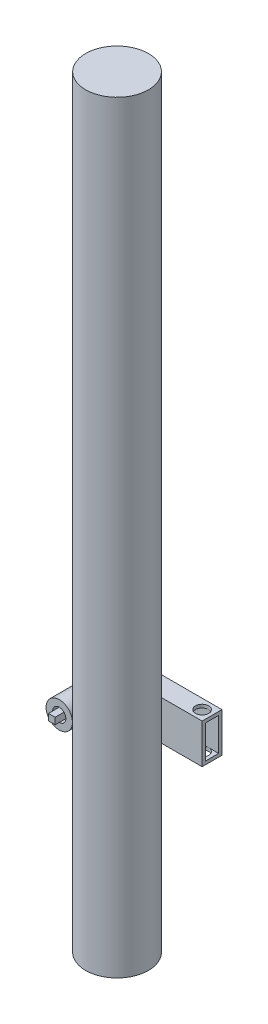
SolidWorks part; units mm, degrees
ref_plane "Front Plane" through (0, 0, 0) normal (0, 0, 1) x (1, 0, 0)
ref_plane "Top Plane" through (0, 0, 0) normal (0, 1, 0) x (1, 0, 0)
ref_plane "Right Plane" through (0, 0, 0) normal (1, 0, 0) x (0, 0, -1)
sketch "Elevation Bar" plane through (0, 0, 0) normal (0, 1, 0) x (1, 0, 0)
  circle A0 centre (0, 0) radius 30.226
  dimension "D1" = 60.452
extrude "Elevation Bar Part" add sketch "Elevation Bar" along normal blind 734.06
sketch "Pole and Drivetrain Pos" plane through (0, 0, 0) normal (0, 0, 1) x (1, 0, 0)
  line L0 (0, 0) -> (172.1794, 0) construction
  line L1 (-30.226, 0) -> (-30.226, 734.06) construction
  line L2 (-30.226, 734.06) -> (30.226, 734.06) construction
  line L3 (30.226, 734.06) -> (30.226, 0) construction
  line L4 (30.226, 0) -> (30.226, 734.06) construction
  line L5 (636.651, 41.275) -> (27.051, 41.275) construction
  line L6 (636.651, 53.975) -> (27.051, 53.975)
  line L7 (636.651, 53.975) -> (636.651, 28.575)
  line L8 (636.651, 28.575) -> (27.051, 28.575)
  line L9 (27.051, 53.975) -> (27.051, 28.575)
  line L10 (-30.226, 93.98) -> (30.226, 93.98) construction
  line L11 (33.2486, 0) -> (-33.2486, 0) construction
  line L12 (30.226, 185.42) -> (-30.226, 185.42) construction
  line L13 (30.226, 276.86) -> (-30.226, 276.86) construction
  line L14 (30.226, 368.3) -> (-30.226, 368.3) construction
  line L15 (30.226, 459.74) -> (-30.226, 459.74) construction
  line L16 (30.226, 551.18) -> (-30.226, 551.18) construction
  line L17 (30.226, 642.62) -> (-30.226, 642.62) construction
  line L18 (30.226, 73.152) -> (750.8896, 73.152) construction
  circle A0 centre (579.501, 41.275) radius 41.275 construction
  circle A1 centre (84.201, 41.275) radius 41.275 construction
  circle A2 centre (331.851, 41.275) radius 41.275 construction
  circle A3 centre (84.201, 41.275) radius 25.4
  point P24 (331.851, 41.275)
  point P28 (0, 0)
  point P45 (0, 0)
  dimension "D2" = 82.55
  dimension "D5" = 50.8
  dimension "D1" = 609.6
  dimension "D3" = 25.4
  dimension "D6" = 93.98
  dimension "D7" = 185.42
  dimension "D8" = 276.86
  dimension "D9" = 368.3
  dimension "D10" = 459.74
  dimension "D11" = 551.18
  dimension "D12" = 642.62
  dimension "D13" = 73.152
  dimension "D14" = 57.15
  dimension "D4" = 57.15
  dimension "D15" = 6.35
sketch "Driving Wheels Geo" plane through (0, 0, 0) normal (0, 0, 1) x (1, 0, 0)
  line L0 (-30.226, 182.88) -> (-30.226, 101.727) construction
  line L1 (55.626, 101.727) -> (30.226, 101.727) construction
  line L2 (-30.226, 0) -> (-30.226, 734.06) construction
  line L3 (30.226, 734.06) -> (30.226, 0) construction
  line L5 (30.226, 101.727) -> (-30.226, 101.727) construction
  line L6 (-30.226, 182.88) -> (30.226, 101.727) construction
  line L7 (31.8135, 101.727) -> (-30.226, 182.88) construction
  line L8 (30.226, 227.417) -> (203.668, 53.975) construction
  line L9 (-42.926, 195.58) -> (44.8729, 195.58) construction
  line L10 (30.226, 73.152) -> (750.8896, 73.152) construction
  line L11 (636.651, 53.975) -> (27.051, 53.975) construction
  line L14 (-42.926, 170.18) -> (44.8729, 170.18) construction
  line L15 (44.8729, 170.18) -> (44.8729, 195.58) construction
  line L16 (81.026, 28.575) -> (81.026, 257.175) construction
  line L17 (32.1729, 195.58) -> (57.5729, 195.58) construction
  line L18 (32.1729, 195.58) -> (32.1729, 170.18) construction
  line L19 (32.1729, 170.18) -> (57.5729, 170.18) construction
  line L20 (57.5729, 195.58) -> (57.5729, 170.18) construction
  line L21 (32.1729, 195.58) -> (57.5729, 170.18) construction
  line L22 (32.1729, 170.18) -> (57.5729, 195.58) construction
  line L23 (636.651, 28.575) -> (27.051, 28.575) construction
  line L24 (284.226, 257.175) -> (81.026, 257.175) construction
  line L25 (284.226, 257.175) -> (284.226, 53.975) construction
  line L26 (81.026, 257.175) -> (30.226, 257.175) construction
  circle A1 centre (55.626, 101.727) radius 25.4
  circle A3 centre (-42.926, 182.88) radius 12.7
  circle A4 centre (81.026, 104.775) radius 50.8 construction
  circle A5 centre (55.626, 101.727) radius 23.8125 construction
  circle A7 centre (284.226, 257.175) radius 203.2 construction
  point P28 (44.8729, 182.88)
  dimension "D1" = 50.8
  dimension "D2" = 1.5875
  dimension "D3" = 52.603
  dimension "D4" = 3.175
  dimension "D5" = 182.88
  dimension "D8" = 101.6
  dimension "D6" = 25.4
  dimension "D13" = 3.175
  dimension "D14" = 50.8
  dimension "D16" = 406.4
  dimension "D7" = 81.153
  dimension "D9" = 45
  dimension "D10" = 53.317
  dimension "D11" = 25.4
  dimension "D12" = 47.752
ref_plane "Plane1" through (0, 182.88, 0) normal (0, 1, 0) x (1, 0, 0)
sketch "Clamp Geo" plane through (0, 182.88, 0) normal (0, 1, 0) x (1, 0, 0)
  line L0 (-42.926, -19.8438) -> (-42.926, 50.8635) construction
  line L3 (27.051, 228.6) -> (27.051, -228.6) construction
  line L4 (50.0464, 31.8135) -> (-49.276, 31.8135)
  line L5 (50.0464, 31.8135) -> (50.0464, 50.8635)
  line L6 (50.0464, 50.8635) -> (-49.276, 50.8635)
  line L7 (-49.276, 31.8135) -> (-49.276, 50.8635)
  line L10 (-46.101, 50.8635) -> (-39.751, 50.8635)
  line L11 (-46.101, 50.8635) -> (-46.101, -19.8438)
  line L12 (-46.101, -19.8438) -> (-39.751, -19.8438)
  line L13 (-39.751, 50.8635) -> (-39.751, -19.8438)
  line L14 (-55.626, 12.7) -> (-30.226, 12.7) construction
  line L15 (-55.626, 12.7) -> (-55.626, -12.7) construction
  line L16 (-55.626, -12.7) -> (-30.226, -12.7) construction
  line L17 (-30.226, 12.7) -> (-30.226, -12.7) construction
  line L18 (-55.626, 12.7) -> (-30.226, -12.7) construction
  line L19 (-55.626, -12.7) -> (-30.226, 12.7) construction
  line L20 (0, -30.226) -> (0, 30.226) construction
  line L21 (-30.226, 0) -> (30.226, 0) construction
  line L22 (-46.101, 46.101) -> (-42.926, 46.101) construction
  line L23 (-39.751, 41.3385) -> (-46.101, 41.3385)
  line L24 (-46.101, 41.3385) -> (-46.101, 50.8635) construction
  line L25 (-39.751, 31.8135) -> (-39.751, 50.8635) construction
  line L26 (50.0464, 41.3385) -> (40.5214, 41.3385) construction
  circle A0 centre (0, 0) radius 30.226 construction
  circle A3 centre (-42.926, 46.101) radius 1.8288
  circle A5 centre (-42.926, 36.576) radius 1.8288
  circle A6 centre (40.5214, 41.3385) radius 6.35
  circle A7 centre (40.5214, 41.3385) radius 13.4704 construction
  point P14 (-42.926, 0)
  point P32 (-39.751, 41.3385)
  point P34 (-46.101, 41.3385)
  point P36 (-42.926, 41.3385)
  point P42 (50.0464, 41.3385)
  dimension "D1" = 60.452
  dimension "D4" = 1.5875
  dimension "D7" = 3.6576
  dimension "D8" = 3.175
  dimension "D10" = 12.7
  dimension "D11" = 3.175
  dimension "D2" = 457.2
  dimension "D3" = 19.05
  dimension "D5" = 6.35
  dimension "D6" = 25.4
  dimension "D9" = 99.3224
  dimension "D13" = 7.1437
sketch "Locked Setting Geo" plane through (0, 182.88, 0) normal (0, 1, 0) x (1, 0, 0)
  line L0 (30.2525, 144.301) -> (91.1428, 108.3583) construction
  line L1 (27.477, 37.9778) -> (77.9656, 123.5104)
  line L2 (27.477, 37.9778) -> (43.8821, 28.2941)
  line L3 (43.8821, 28.2941) -> (94.3707, 113.8267)
  line L4 (77.9656, 123.5104) -> (94.3707, 113.8267)
  line L5 (92.7568, 111.0925) -> (89.5289, 105.6242)
  line L6 (92.7568, 111.0925) -> (31.8664, 147.0352)
  line L7 (31.8664, 147.0352) -> (28.6385, 141.5668)
  line L8 (89.5289, 105.6242) -> (28.6385, 141.5668)
  line L9 (64.7337, 138.6948) -> (51.8221, 116.8213) construction
  line L10 (64.7337, 138.6948) -> (42.8602, 151.6064) construction
  line L11 (42.8602, 151.6064) -> (29.9486, 129.7329) construction
  line L12 (51.8221, 116.8213) -> (29.9486, 129.7329) construction
  line L13 (64.7337, 138.6948) -> (29.9486, 129.7329) construction
  line L14 (42.8602, 151.6064) -> (51.8221, 116.8213) construction
  line L17 (88.6555, 113.5135) -> (87.0416, 110.7793) construction
  line L18 (81.3263, 110.466) -> (84.5542, 115.9344)
  line L19 (84.5542, 115.9344) -> (92.7568, 111.0925) construction
  line L20 (73.1238, 115.3079) -> (89.5289, 105.6242) construction
  line L21 (35.6795, 33.1359) -> (40.5214, 41.3385) construction
  line L22 (50.0464, 50.8635) -> (-49.276, 50.8635) construction
  line L23 (-46.101, 50.8635) -> (-46.101, -19.8438) construction
  line L24 (27.051, 228.6) -> (27.051, -228.6) construction
  circle A1 centre (87.0416, 110.7793) radius 1.8288
  circle A2 centre (78.839, 115.6211) radius 1.8288
  circle A3 centre (40.5214, 41.3385) radius 6.35
  point P10 (47.3411, 134.2138)
  point P28 (81.3263, 110.466)
  point P30 (84.5542, 115.9344)
  point P32 (82.9403, 113.2002)
  point P36 (35.6795, 33.1359)
  point P40 (40.5214, 41.3385)
  point P44 (-17.1792, 28.8062)
  dimension "D6" = 3.6576
  dimension "D9" = 12.7
  dimension "D2" = 19.05
  dimension "D3" = 1.5875
  dimension "D4" = 6.35
  dimension "D5" = 25.4
  dimension "D7" = 3.175
  dimension "D8" = 99.3224
  dimension "D10" = 3.175
  dimension "D11" = 50.8635
  dimension "D12" = 67.3197
extrude "Boss-Extrude1" add sketch "Clamp Geo" along normal blind 19.05 and the other way blind 19.05 separate body contours L6 L13 L4 L5 A6 | L11 L6 L7 L4 | L13 L23 L11 L4 A5 | L23 L13 L6 L11 A3 region at (2.3187, 182.88, -41.3385) region at (-42.926, 182.88, -31.928) region at (-47.6885, 182.88, -41.3385) region at (-42.926, 182.88, -41.453)
sketch "Sketch2" plane through (-49.276, 0, 0) normal (-1, 0, 0) x (0, 0, 1)
  line L0 (-41.3385, 201.93) -> (-41.3385, 163.83) construction
  line L1 (-31.8135, 201.93) -> (-50.8635, 201.93) construction
  line L2 (-31.8135, 163.83) -> (-50.8635, 163.83) construction
  line L3 (-31.8135, 163.83) -> (-31.8135, 201.93) construction
  line L4 (-47.6885, 167.005) -> (-34.9885, 167.005)
  line L5 (-47.6885, 167.005) -> (-47.6885, 198.755)
  line L6 (-47.6885, 198.755) -> (-34.9885, 198.755)
  line L7 (-34.9885, 167.005) -> (-34.9885, 198.755)
  line L8 (-47.6885, 167.005) -> (-34.9885, 198.755) construction
  line L9 (-47.6885, 198.755) -> (-34.9885, 167.005) construction
  point P6 (-41.3385, 182.88)
  dimension "D1" = 3.175
  dimension "D2" = 3.175
extrude "Cut-Extrude2" cut sketch "Sketch2" against normal up to surface (99.3224 mm away) up to face at (50.0464, 182.88, -41.3385)
sketch "Sketch3" plane through (0, 0, -50.8635) normal (0, 0, -1) x (-1, 0, 0)
  line L2 (39.7129, 179.6669) -> (46.1391, 179.6669)
  line L3 (39.7129, 179.6669) -> (39.7129, 186.0931)
  line L4 (39.7129, 186.0931) -> (46.1391, 186.0931)
  line L5 (46.1391, 179.6669) -> (46.1391, 186.0931)
  line L6 (39.7129, 179.6669) -> (46.1391, 186.0931) construction
  line L7 (39.7129, 186.0931) -> (46.1391, 179.6669) construction
  point P0 (42.926, 182.88)
  point P1 (42.926, 182.88)
  dimension "D1" = 6.4262
extrude "Cut-Extrude3" cut sketch "Sketch3" against normal up to surface (19.05 mm away) up to face at (0.3852, 182.88, -31.8135)
extrude "Boss-Extrude2" add sketch "Clamp Geo<3>" along normal blind 3.175 and the other way blind 3.175 separate body contours L13 L4 L11 L12 | L13 L23 L11 L4 A5 | L23 L13 L6 L11 A3 region at (-42.926, 182.88, -5.9849) region at (-42.926, 182.88, -31.928) region at (-42.926, 182.88, -41.453)
sketch "Clamp Geo<3>" plane through (0, 182.88, 0) normal (0, 1, 0) x (1, 0, 0) same geometry as "Clamp Geo"
sketch "Custom Driven Flywheel" plane through (0, 0, 0) normal (0, 0, 1) x (1, 0, 0)
  circle A0 centre (-42.926, 182.88) radius 12.7 construction
  circle A1 centre (-42.926, 182.88) radius 12.7
  circle A2 centre (-42.926, 182.88) radius 6.35
  dimension "D1" = 12.7
extrude "Boss-Extrude3" add sketch "Custom Driven Flywheel" along normal mid plane 25.4 separate body
sketch "Sketch8" plane through (0, 167.005, 0) normal (0, 1, 0) x (1, 0, 0)
  line L0 (-42.926, 47.6885) -> (-42.926, 34.9885) construction
  line L1 (-49.276, 34.9885) -> (-36.576, 34.9885) construction
  line L2 (-49.276, 34.9885) -> (-49.276, 47.6885)
  line L3 (-49.276, 47.6885) -> (-36.576, 47.6885) construction
  line L4 (-36.576, 34.9885) -> (-36.576, 47.6885)
  line L5 (-36.576, 41.3385) -> (-42.926, 41.3385) construction
  line L6 (-42.926, 41.3385) -> (-49.276, 41.3385) construction
  line L7 (-43.8339, 34.9885) -> (-49.276, 34.9885)
  line L8 (-43.8339, 47.6885) -> (-49.276, 47.6885)
  line L9 (-42.0181, 34.9885) -> (-36.576, 34.9885)
  line L10 (-42.0181, 47.6885) -> (-36.576, 47.6885)
  arc A0 (-43.8339, 47.6885) -> (-42.0181, 47.6885) centre (-42.926, 46.101) ccw construction
  arc A2 (-42.0181, 34.9885) -> (-43.8339, 34.9885) centre (-42.926, 36.576) ccw construction
  arc A3 (-43.8339, 47.6885) -> (-42.0181, 47.6885) centre (-42.926, 46.101) ccw
  arc A4 (-42.0181, 34.9885) -> (-43.8339, 34.9885) centre (-42.926, 36.576) ccw
extrude "Boss-Extrude5" add sketch "Sketch8" along normal up to surface (15.875 mm away) separate body up to plane "Plane1"
sketch "Sketch10" plane through (0, 182.88, 0) normal (0, 1, 0) x (1, 0, 0)
  line L0 (-36.576, 41.3385) -> (-49.276, 41.3385) construction
  line L1 (-36.576, 34.9885) -> (-36.576, 47.6885) construction
  line L2 (-49.276, 47.6885) -> (-49.276, 34.9885) construction
  line L3 (-49.276, 34.9885) -> (-43.8339, 34.9885) construction
  line L4 (-46.1391, 34.9885) -> (-39.7129, 34.9885)
  line L5 (-46.1391, 34.9885) -> (-46.1391, 47.6885)
  line L6 (-46.1391, 47.6885) -> (-39.7129, 47.6885)
  line L7 (-39.7129, 34.9885) -> (-39.7129, 47.6885)
  line L8 (-46.1391, 34.9885) -> (-39.7129, 47.6885) construction
  line L9 (-46.1391, 47.6885) -> (-39.7129, 34.9885) construction
  point P6 (-42.926, 41.3385)
  dimension "D1" = 6.4262
extrude "Cut-Extrude5" cut sketch "Sketch10" against normal blind 6.3881
ref_plane "Plane2" through (0, 0, 210.82) normal (0, 0, 1) x (1, 0, 0)
ref_plane "Plane3" through (0, 0, 166.37) normal (0, 0, 1) x (1, 0, 0)
sketch "Sketch12" plane through (0, 0, 166.37) normal (0, 0, 1) x (1, 0, 0)
  line L0 (636.651, 41.275) -> (27.051, 41.275) construction
  line L1 (636.651, 41.275) -> (27.051, 41.275) construction
  line L5 (636.651, 53.975) -> (27.051, 53.975) construction
  circle A0 centre (84.201, 41.275) radius 25.4 construction
  circle A1 centre (84.201, 41.275) radius 25.4
  circle A2 centre (55.626, 101.727) radius 21.1667
  circle A4 centre (83.7633, 116.4361) radius 10.5833
  circle A5 centre (128.651, 41.275) radius 19.05
  circle A7 centre (83.7633, 116.4361) radius 21.1667
  circle A8 centre (100.4306, 89.4127) radius 10.5833
  circle A9 centre (100.4306, 89.4127) radius 25.4
  point P3 (55.626, 101.727)
  dimension "D1" = 42.3333
  dimension "D2" = 21.1667
  dimension "D3" = 50.8
  dimension "D4" = 38.1
  dimension "D5" = 42.3333
  dimension "D6" = 21.1667
  dimension "D7" = 10.0377
equation "\"D4@Pole and Drivetrain Pos\"=\"D14@Pole and Drivetrain Pos\""
